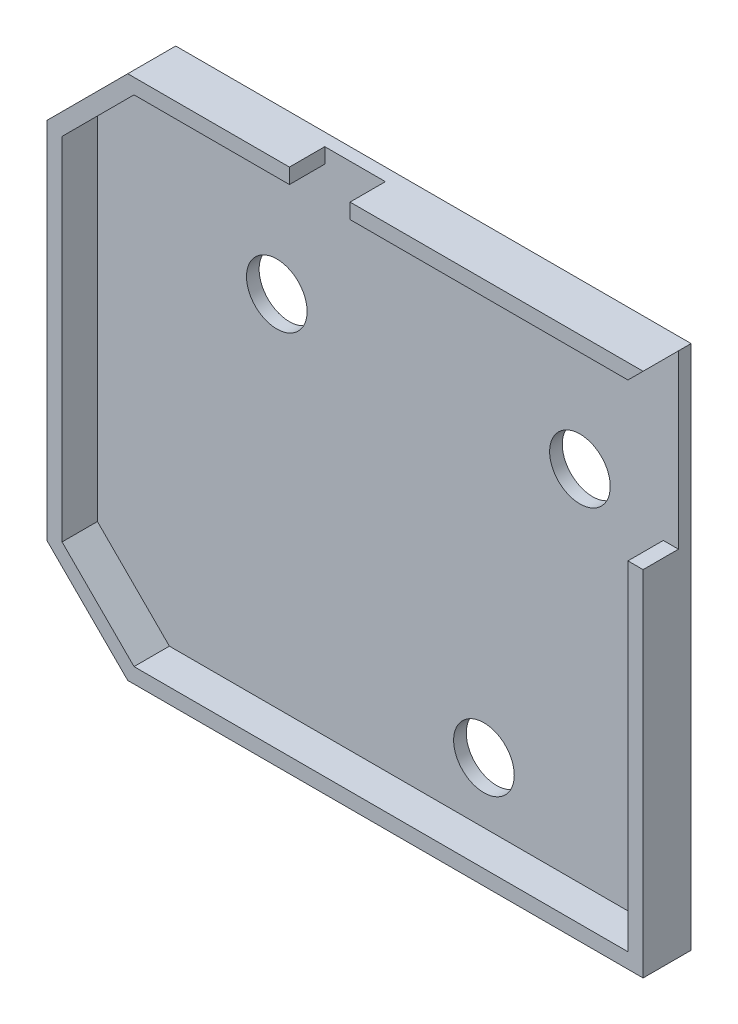
SolidWorks part; units mm, degrees
ref_plane "Plan de face" through (0, 0, 0) normal (0, 0, 1) x (1, 0, 0)
ref_plane "Plan de dessus" through (0, 0, 0) normal (0, 1, 0) x (1, 0, 0)
ref_plane "Plan de droite" through (0, 0, 0) normal (1, 0, 0) x (0, 0, -1)
sketch "Esquisse1" plane through (0, 0, 0) normal (0, 0, 1) x (1, 0, 0)
  line L0 (0, -85) -> (16, -101)
  line L4 (118, 3) -> (118, -101)
  line L5 (16, 3) -> (0, -13)
  line L7 (118, 3) -> (16, 3)
  line L8 (0, -13) -> (0, -85)
  line L9 (16, -101) -> (118, -101)
  dimension "D1" = 104
  dimension "D2" = 118
  dimension "D3" = 16
  dimension "D4" = 16
  dimension "D5" = 16
  dimension "D6" = 16
extrude "Boss.-Extru.1" add sketch "Esquisse1" along normal blind 2.5
sketch "Esquisse2" plane through (0, 0, 2.5) normal (0, 0, 1) x (1, 0, 0)
  line L0 (0, -13) -> (0, -85) construction
  line L1 (3, 0) -> (115, 0) construction
  line L2 (3, 0) -> (3, -98) construction
  line L3 (3, -98) -> (115, -98) construction
  line L4 (115, 0) -> (115, -98) construction
  line L5 (16, -101) -> (118, -101) construction
  line L6 (118, -101) -> (118, 3) construction
  line L7 (118, 3) -> (16, 3) construction
  line L8 (115, -31) -> (118, -31)
  line L9 (3, -83.7574) -> (17.2426, -98)
  line L10 (0, -85) -> (16, -101) construction
  line L11 (3, -14.2426) -> (17.2426, 0)
  line L12 (16, 3) -> (0, -13) construction
  line L14 (3, -14.2426) -> (3, -83.7574)
  line L15 (17.2426, -98) -> (115, -98)
  line L16 (118, 3) -> (118, -101) construction
  line L17 (118, -101) -> (16, -101)
  line L18 (16, -101) -> (0, -85)
  line L19 (0, -85) -> (0, -13)
  line L20 (0, -13) -> (16, 3)
  line L22 (115, 0) -> (118, 3)
  line L23 (115, -98) -> (115, -31)
  line L24 (118, -31) -> (118, -101)
  line L25 (48, 0) -> (48, 3)
  line L26 (60, 0) -> (60, 3)
  line L27 (17.2426, 0) -> (48, 0)
  line L28 (48, 3) -> (16, 3)
  line L29 (60, 3) -> (118, 3)
  line L30 (115, 0) -> (60, 0)
  point P33 (48, 0)
  point P34 (60, 0)
  dimension "D1" = 3
  dimension "D2" = 3
  dimension "D3" = 3
  dimension "D4" = 3
  dimension "D5" = 3
  dimension "D6" = 3
  dimension "D7" = 70
  dimension "D8" = 45
  dimension "D9" = 12
extrude "Boss.-Extru.2" add sketch "Esquisse2" along normal blind 7
sketch "Esquisse3" plane through (0, 0, 2.5) normal (0, 0, 1) x (1, 0, 0)
  line L0 (115, -31) -> (115, -98) construction
  line L2 (3, -83.7574) -> (3, -14.2426) construction
  line L3 (115, -31) -> (115, -98) construction
  line L4 (115, -98) -> (17.2426, -98) construction
  line L5 (60, 3) -> (48, 3) construction
  circle A0 centre (98.5, -27) radius 6
  circle A1 centre (38.5, -27) radius 6
  circle A2 centre (79.5, -86) radius 6
  dimension "D1" = 16.5
  dimension "D2" = 30
  dimension "D3" = 30
  dimension "D4" = 35.5
  dimension "D5" = 35.5
  dimension "D6" = 12
extrude "Enlèv. mat.-Extru.1" cut sketch "Esquisse3" against normal blind 10
